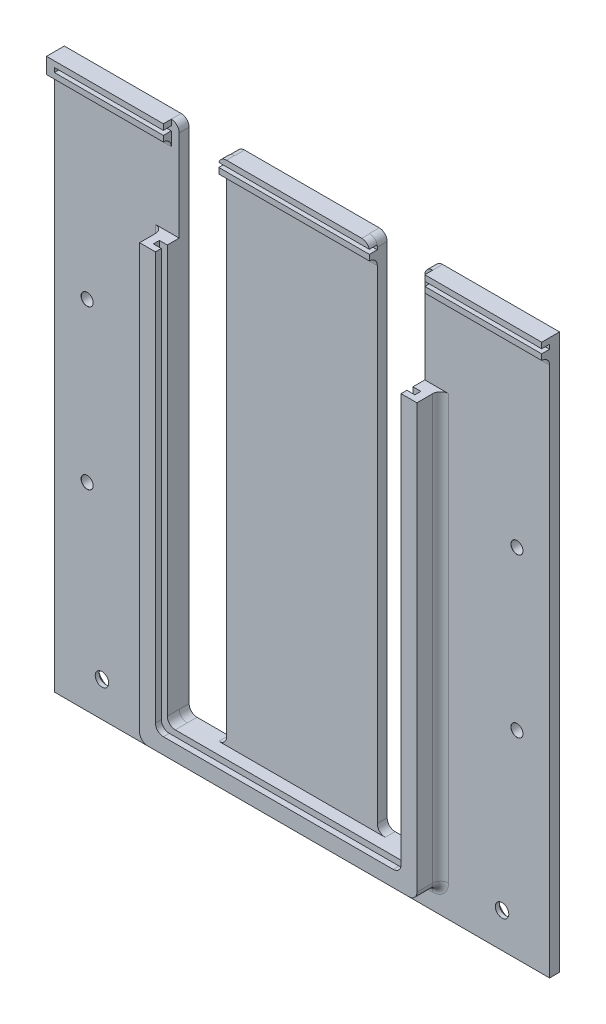
SolidWorks part; units mm, degrees
ref_plane "Plano frontal" through (0, 0, 0) normal (0, 0, 1) x (1, 0, 0)
ref_plane "Plano superior" through (0, 0, 0) normal (0, 1, 0) x (1, 0, 0)
ref_plane "Plano direito" through (0, 0, 0) normal (1, 0, 0) x (0, 0, -1)
other "Centro da massa"
sketch "Esboço1" plane through (0, 0, 0) normal (0, 0, 1) x (1, 0, 0)
  line L0 (10.1406, 22.9022) -> (10.1406, -117.0978) construction
  line L1 (-52.3594, 22.9022) -> (72.6406, 22.9022)
  line L2 (-52.3594, 22.9022) -> (-52.3594, -117.0978)
  line L3 (-52.3594, -117.0978) -> (72.6406, -117.0978)
  line L4 (72.6406, 22.9022) -> (72.6406, -117.0978)
  line L5 (-52.3594, -47.0978) -> (72.6406, -47.0978) construction
  dimension "D1" = 125
  dimension "D2" = 140
extrude "Ressalto-extrusão1" add sketch "Esboço1" along normal blind 2.5
sketch "Esboço2" plane through (0, 0, 2.5) normal (0, 0, 1) x (1, 0, 0)
  line L0 (-52.3594, -47.0978) -> (72.6406, -47.0978) construction
  line L1 (-52.3594, 22.9022) -> (-52.3594, -117.0978) construction
  line L2 (72.6406, -117.0978) -> (72.6406, 22.9022) construction
  line L3 (10.1406, 22.9022) -> (10.1406, -117.0978) construction
  line L4 (72.6406, 22.9022) -> (-52.3594, 22.9022) construction
  line L5 (-52.3594, -117.0978) -> (72.6406, -117.0978) construction
  line L7 (-24.8594, -2.0978) -> (-20.8594, -2.0978)
  line L8 (-24.8594, -2.0978) -> (-24.8594, -107.0978)
  line L9 (-24.8594, -107.0978) -> (-23.8742, -107.0978)
  line L10 (-20.8594, -2.0978) -> (-20.8594, -107.0978)
  line L11 (41.1406, -2.0978) -> (41.1406, -107.0978)
  line L12 (45.1406, -2.0978) -> (41.1406, -2.0978)
  line L13 (45.1406, -2.0978) -> (45.1406, -107.0978)
  line L14 (-20.8594, -107.0978) -> (41.1406, -107.0978)
  line L15 (-24.8594, -107.0978) -> (-23.8742, -107.0978)
  line L16 (-24.8594, -107.0978) -> (-24.8594, -111.0978)
  line L17 (-24.8594, -111.0978) -> (45.1406, -111.0978)
  line L18 (45.1406, -107.0978) -> (45.1406, -111.0978)
  dimension "D1" = 35
  dimension "D2" = 105
  dimension "D3" = 4
  dimension "D4" = 115
  dimension "D5" = 4
extrude "Ressalto-extrusão2" add sketch "Esboço2" along normal blind 6 contours L16 L17 L18 L13 L12 L11 L14 L10 L7 L8
sketch "Esboço3" plane through (41.1406, 0, 0) normal (-1, 0, 0) x (0, 0, 1)
  line L0 (8.5, -2.0978) -> (2.5, -2.0978) construction
  line L1 (5.5, -2.0978) -> (7.02, -2.0978)
  line L2 (5.5, -2.0978) -> (5.5, -107.0978)
  line L3 (5.5, -107.0978) -> (7.02, -107.0978)
  line L4 (7.02, -2.0978) -> (7.02, -107.0978)
  line L5 (8.5, -107.0978) -> (2.5, -107.0978) construction
  line L6 (5.5, -2.0978) -> (0.5363, -2.0978) construction
  line L7 (7.02, -2.0978) -> (8.5, -2.0978) construction
  line L8 (2.5, -2.0978) -> (2.5, -107.0978) construction
  line L9 (8.5, -2.0978) -> (8.5, -107.0978) construction
  dimension "D1" = 1.52
  dimension "D2" = 3
  dimension "D3" = 1.48
extrude "Corte-extrusão1" cut sketch "Esboço3" against normal blind 2
sketch "Esboço4" plane through (-20.8594, 0, 0) normal (1, 0, 0) x (0, 0, -1)
  line L0 (-8.5, -2.0978) -> (-2.5, -2.0978) construction
  line L1 (-7.02, -2.0978) -> (-5.5, -2.0978)
  line L2 (-7.02, -2.0978) -> (-7.02, -107.0978)
  line L3 (-7.02, -107.0978) -> (-5.5, -107.0978)
  line L4 (-5.5, -2.0978) -> (-5.5, -107.0978)
  line L5 (-8.5, -107.0978) -> (-2.5, -107.0978) construction
  line L6 (-8.5, -2.0978) -> (-7.02, -2.0978) construction
  line L7 (-5.5, -2.0978) -> (-2.5, -2.0978) construction
  line L9 (-2.5, -2.0978) -> (-2.5, -107.0978) construction
  line L10 (-8.5, -2.0978) -> (-8.5, -107.0978) construction
  dimension "D1" = 1.52
  dimension "D2" = 3
  dimension "D3" = 1.48
extrude "Corte-extrusão2" cut sketch "Esboço4" against normal blind 2
sketch "Esboço5" plane through (0, -107.0978, 0) normal (0, 1, 0) x (1, 0, 0)
  line L5 (-22.8594, -5.5) -> (43.1406, -5.5)
  line L6 (-22.8594, -5.5) -> (-22.8594, -7.02)
  line L7 (-22.8594, -7.02) -> (43.1406, -7.02)
  line L8 (43.1406, -5.5) -> (43.1406, -7.02)
extrude "Corte-extrusão3" cut sketch "Esboço5" against normal blind 2
fillet "Filete1" radius 2 4 edges at (41.1406, -107.0978, 4) (41.1406, -107.0978, 7.76) (-20.8594, -107.0978, 4) (-20.8594, -107.0978, 7.76)
fillet "Filete2" radius 2 2 edges at (-24.8594, -111.0978, 5.5) (45.1406, -111.0978, 5.5)
fillet "Filete3" radius 2 5 edges at (45.1406, -55.5978, 2.5) (44.5548, -110.512, 2.5) (10.1406, -111.0978, 2.5) (-24.2736, -110.512, 2.5) (-24.8594, -55.5978, 2.5)
sketch "Esboço6" plane through (0, 0, 2.5) normal (0, 0, 1) x (1, 0, 0)
  line L0 (-20.8594, -2.0978) -> (41.1406, -2.0978) construction
  line L1 (10.1406, -2.0978) -> (10.1406, -41.1152) construction
  line L2 (-14.8594, -2.0978) -> (-14.8594, -50.9519) construction
  line L3 (-20.8594, -2.0978) -> (-20.8594, -105.0978) construction
  line L4 (72.6406, 22.9022) -> (-52.3594, 22.9022) construction
  line L5 (-20.8594, 22.9022) -> (-8.8594, 22.9022)
  line L6 (-20.8594, 22.9022) -> (-20.8594, -107.0978)
  line L7 (-20.8594, -107.0978) -> (-8.8594, -107.0978)
  line L8 (-8.8594, 22.9022) -> (-8.8594, -107.0978)
  line L9 (-18.8594, -107.0978) -> (39.1406, -107.0978) construction
  line L10 (41.1406, -107.0978) -> (29.1406, -107.0978)
  line L11 (29.1406, 22.9022) -> (29.1406, -107.0978)
  line L12 (41.1406, 22.9022) -> (29.1406, 22.9022)
  line L13 (41.1406, 22.9022) -> (41.1406, -107.0978)
  dimension "D1" = 6
  dimension "D2" = 12
extrude "Corte-extrusão4" cut sketch "Esboço6" against normal through all
fillet "Filete4" radius 2 4 edges at (-20.8594, 22.9022, 1.25) (-8.8594, 22.9022, 1.25) (29.1406, 22.9022, 1.25) (41.1406, 22.9022, 1.25)
fillet "Filete5" radius 2 4 edges at (41.1406, -107.0978, 1.25) (29.1406, -107.0978, 1.25) (-20.8594, -107.0978, 1.25) (-8.8594, -107.0978, 1.25)
sketch "Esboço7" plane through (0, 0, 2.5) normal (0, 0, 1) x (1, 0, 0)
  line L0 (72.6406, -117.0978) -> (72.6406, 22.9022) construction
  line L1 (-52.3594, 22.9022) -> (72.6406, 22.9022)
  line L2 (-52.3594, 22.9022) -> (-52.3594, 18.9022)
  line L3 (-52.3594, 18.9022) -> (72.6406, 18.9022)
  line L4 (72.6406, 22.9022) -> (72.6406, 18.9022)
  line L5 (-22.8594, 22.9022) -> (-22.8594, 18.9022)
  line L6 (10.1406, 22.9022) -> (10.1406, 18.9022) construction
  line L7 (43.1406, 22.9022) -> (43.1406, 18.9022)
  line L8 (-8.8692, 18.9022) -> (-8.8692, 22.9022)
  line L9 (29.1406, 18.9022) -> (29.1406, 22.9022)
  line L10 (29.1406, 20.9022) -> (29.1406, -105.0978) construction
  line M9 (-22.8594, 22.9022) -> (-52.3594, 22.9022)
  line M10 (-52.3594, 22.9022) -> (-52.3594, -117.0978)
  line M12 (72.6406, -117.0978) -> (72.6406, 22.9022)
  line M13 (72.6406, 22.9022) -> (43.1406, 22.9022)
  dimension "D1" = 4
extrude "Ressalto-extrusão3" add sketch "Esboço7" along normal blind 2 contours L6 L1 L8 L3 | L1 L6 L3 L9 | L5 L3 M9 M10 | L7 L3 M13 M12 region at (-37.6094, 20.9022, 2.5) region at (0.6357, 20.9022, 2.5) region at (19.6406, 20.9022, 2.5) region at (57.8906, 20.9022, 2.5)
sketch "Esboço8" plane through (0, 0, 4.5) normal (0, 0, 1) x (1, 0, 0)
  line L0 (72.6406, 18.9022) -> (72.6406, 22.9022) construction
  line L1 (-50.3594, 21.4522) -> (72.6406, 21.4522)
  line L2 (-50.3594, 21.4522) -> (-50.3594, 20.3522)
  line L3 (-50.3594, 20.3522) -> (72.6406, 20.3522)
  line L4 (72.6406, 21.4522) -> (72.6406, 20.3522)
  line L5 (72.6406, 22.9022) -> (72.6406, 21.4522) construction
  line L6 (72.6406, 20.3522) -> (72.6406, 18.9022) construction
  line L7 (-52.3594, 22.9022) -> (-52.3594, 18.9022) construction
  dimension "D1" = 1.1
  dimension "D2" = 2
extrude "Corte-extrusão5" cut sketch "Esboço8" against normal blind 2
fillet "Filete6" radius 2 5 edges at (57.8906, 18.9022, 2.5) (10.1406, 18.9022, 2.5) (-37.6094, 18.9022, 2.5) (29.1406, 22.9022, 3.5) (-8.8692, 22.9022, 3.5)
sketch "Esboço9" plane through (0, 0, 2.5) normal (0, 0, 1) x (1, 0, 0)
  line L0 (10.1357, 22.9022) -> (10.1406, -117.0978) construction
  line L1 (-6.9463, 22.9022) -> (27.2177, 22.9022) construction
  line L2 (-52.3594, -117.0978) -> (72.6406, -117.0978) construction
  line L3 (-52.3594, -50.0978) -> (72.6406, -50.0978) construction
  line L4 (-52.3594, 16.9022) -> (-52.3594, -117.0978) construction
  line L5 (72.6406, -117.0978) -> (72.6406, 16.9022) construction
  line L6 (-44.1094, -50.0978) -> (-44.1094, -1.2846) construction
  line L7 (-44.1094, -27.0978) -> (-52.3594, -27.0978) construction
  line L8 (-52.3594, -24.0978) -> (-52.3594, -30.0978)
  line L9 (-52.3594, -24.0978) -> (-39.8594, -24.0978)
  line L10 (-52.3594, -24.0978) -> (-52.3594, -30.0978)
  line L11 (-52.3594, -30.0978) -> (-39.8594, -30.0978)
  line L12 (-39.8594, -24.0978) -> (-39.8594, -30.0978)
  line L14 (-39.8594, -70.0978) -> (-39.8594, -64.0978)
  line L18 (-52.3594, -64.0978) -> (-39.8594, -64.0978)
  line L19 (-52.3594, -64.0978) -> (-52.3594, -70.0978)
  line L20 (-52.3594, -70.0978) -> (-39.8594, -70.0978)
  line L21 (72.6369, -64.0935) -> (72.6373, -70.0935)
  line L22 (72.6369, -64.0935) -> (60.1369, -64.0943)
  line L23 (60.1373, -70.0943) -> (60.1369, -64.0943)
  line L24 (72.6373, -70.0935) -> (60.1373, -70.0943)
  line L25 (72.6345, -30.0935) -> (60.1345, -30.0943)
  line L26 (60.1341, -24.0943) -> (60.1345, -30.0943)
  line L27 (72.6341, -24.0935) -> (60.1341, -24.0943)
  line L28 (72.6341, -24.0935) -> (72.6345, -30.0935)
  line L29 (-44.1094, -50.0978) -> (-44.1094, -70.0978) construction
  line L30 (-52.3594, -67.0978) -> (-39.8594, -67.0978) construction
  line L31 (64.3906, 16.9022) -> (64.3906, -70.094) construction
  line L32 (72.6406, 16.9022) -> (43.1406, 16.9022) construction
  line L33 (60.1343, -27.0943) -> (72.6343, -27.0935) construction
  line L34 (60.1371, -67.0943) -> (72.6371, -67.0935) construction
  point P21 (-39.8594, -27.0978)
  point P25 (-39.8594, -67.0978)
  point P37 (-44.1094, -67.0978)
  point P46 (64.3906, -27.094)
  point P47 (64.3906, -67.094)
  dimension "D3" = 17
  dimension "D1" = 8.25
  dimension "D2" = 23
  dimension "D4" = 6
  dimension "D5" = 12.5
  dimension "D6" = 6
  dimension "D7" = 12.5
  dimension "D8" = 8.25
hole_wizard "Furos-guia com Ø3.0mm1" positions "Esboço10" profile "Esboço11" hole size "Ø3.0" standard "ISO" end condition through all
sketch "Esboço10" plane through (0, 0, 2.5) normal (0, 0, 1) x (1, 0, 0)
  point P0 (-44.1094, -27.0978)
  point P3 (-44.1094, -67.0978)
  point P6 (64.3906, -27.094)
  point P9 (64.3906, -67.094)
sketch "Esboço11" plane through (-44.1094, -27.0978, 2.5) normal (1, 0, 0) x (0, -1, 0)
  line L0 (0, 0) -> (0, 2.5)
  line L1 (0, 2.5) -> (1.5, 2.5)
  line L2 (1.5, 2.5) -> (1.5, 0.025)
  line L3 (1.5, 0.025) -> (1.525, 0)
  line L5 (1.525, 0) -> (0, 0)
  line L6 (-1.5, 0.025) -> (-1.525, 0) construction
  line L11 (0, -6.35) -> (0, 107.95) construction
  dimension "Thru Hole Dia." = 3
  dimension "Thru Hole Depth" = 2.5
  dimension "Near C'Sink Dia." = 3.05
  dimension "Near C'Sink Angle" = 90
sketch "Esboço12" plane through (0, 0, 0) normal (0, 0, -1) x (-1, 0, 0)
  line L0 (-10.1406, -117.0978) -> (-10.1406, -88.6993) construction
  line L1 (52.3594, -117.0978) -> (-72.6406, -117.0978) construction
  line L2 (-72.6406, -108.2978) -> (-60.6406, -108.2978) construction
  line L3 (-72.6406, -117.0978) -> (-72.6406, 22.9022) construction
  line L4 (-60.6406, -108.2978) -> (-60.6406, -117.0978) construction
  circle A0 centre (-60.6406, -108.2978) radius 2.8052
  circle A1 centre (40.3594, -108.2978) radius 2.8052
  dimension "D1" = 12
  dimension "D2" = 8.8
hole_wizard "Rebaixo para parafuso com cabeça panela de M31" positions "Esboço13" profile "Esboço14" counterbore size "M3" standard "ISO" end condition through all
sketch "Esboço13" plane through (0, 0, 0) normal (0, 0, -1) x (-1, 0, 0)
  point P0 (40.3594, -108.2978)
  point P3 (-60.6406, -108.2978)
sketch "Esboço14" plane through (-40.3594, -108.2978, 0) normal (1, 0, 0) x (0, 1, 0)
  line L0 (0, 0) -> (0, 8.5)
  line L1 (0, 8.5) -> (1.7, 8.5)
  line L3 (1.7, 8.5) -> (1.7, 1.5)
  line L4 (3.5, 1.5) -> (1.7, 1.5)
  line L5 (3.5, 1.5) -> (3.5, 0.025)
  line L6 (3.5, 0.025) -> (3.525, 0)
  line L7 (3.525, 0) -> (0, 0)
  line L8 (-3.5, 0.025) -> (-3.525, 0) construction
  line L11 (0, -6.35) -> (0, 107.95) construction
  dimension "Thru Hole Dia." = 3.4
  dimension "Thru Hole Depth" = 8.5
  dimension "C'Bore Dia." = 7
  dimension "C'Bore Depth" = 1.5
  dimension "Near C'Sink Dia." = 7.05
  dimension "Near C'Sink Angle" = 90
